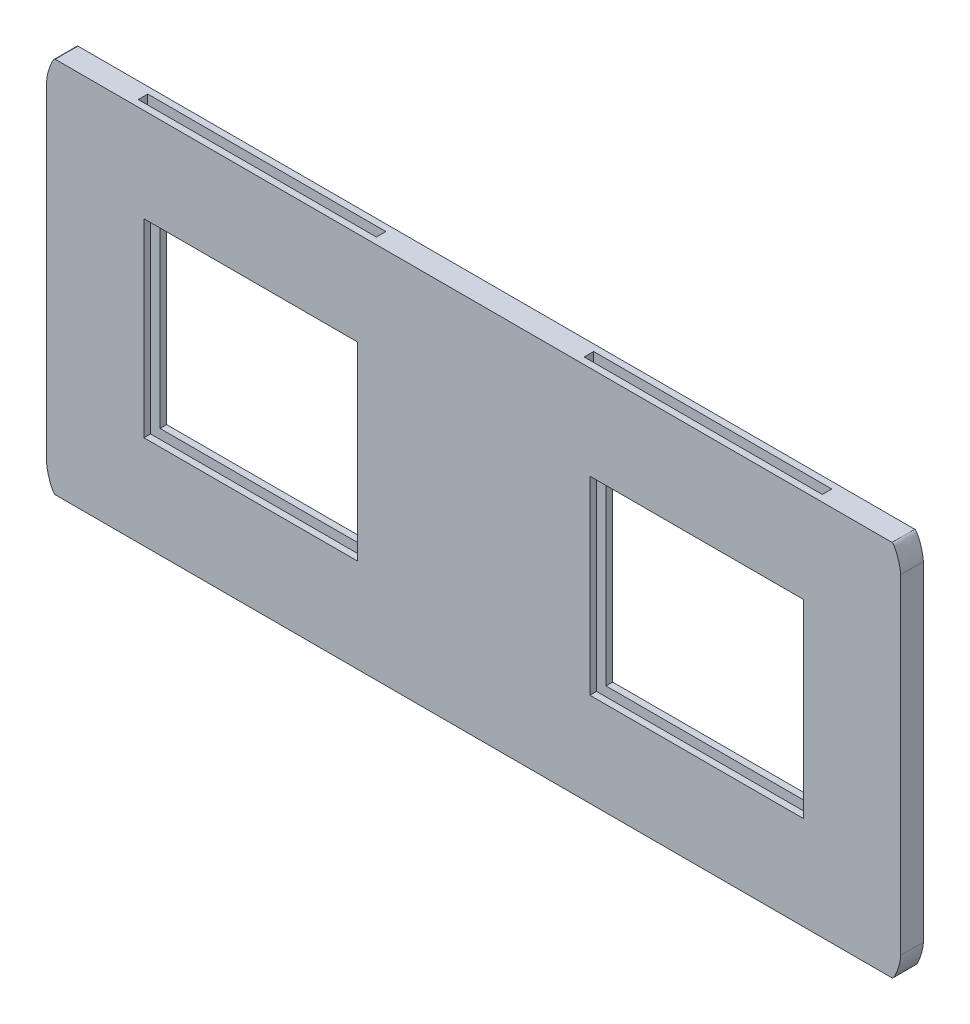
SolidWorks part; units mm, degrees
ref_plane "前视基准面" through (0, 0, 0) normal (0, 0, 1) x (1, 0, 0)
ref_plane "上视基准面" through (0, 0, 0) normal (0, 1, 0) x (1, 0, 0)
ref_plane "右视基准面" through (0, 0, 0) normal (1, 0, 0) x (0, 0, -1)
sketch "草图1" plane through (0, 0, 0) normal (0, 0, 1) x (1, 0, 0)
  line L1 (-90, 39.75) -> (90, 39.75)
  line L2 (-90, 39.75) -> (-90, -39.75)
  line L3 (-90, -39.75) -> (90, -39.75)
  line L4 (90, 39.75) -> (90, -39.75)
  line L5 (-90, 39.75) -> (90, -39.75) construction
  line L6 (-90, -39.75) -> (90, 39.75) construction
  point P0 (0, 0)
  dimension "D1" = 180
  dimension "D2" = 79.5
extrude "凸台-拉伸1" add sketch "草图1" along normal mid plane 4.8
sketch "草图2" plane through (0, 0, 2.4) normal (0, 0, 1) x (1, 0, 0)
  line L0 (0, 0) -> (0, -20.626) construction
  line L1 (-65, 12) -> (-29, 12) construction
  line L2 (-65, 12) -> (-65, -12) construction
  line L3 (-65, -12) -> (-29, -12) construction
  line L4 (-29, 12) -> (-29, -12) construction
  line L5 (-65, 12) -> (-29, -12) construction
  line L6 (-65, -12) -> (-29, 12) construction
  line L7 (65, -12) -> (29, 12) construction
  line L8 (65, 12) -> (29, -12) construction
  line L9 (29, 12) -> (29, -12) construction
  line L10 (65, -12) -> (29, -12) construction
  line L11 (65, 12) -> (65, -12) construction
  line L12 (65, 12) -> (29, 12) construction
  line L13 (-90, 39.75) -> (-90, -39.75) construction
  line L15 (-72, 25) -> (-22, 25) construction
  line L16 (-72, 25) -> (-72, -25) construction
  line L17 (-72, -25) -> (-22, -25) construction
  line L18 (-22, 25) -> (-22, -25) construction
  line L19 (-72, 25) -> (-22, -25) construction
  line L20 (-72, -25) -> (-22, 25) construction
  point P0 (-47, 0)
  point P12 (47, 0)
  point P15 (-47, 0)
  dimension "D1" = 36
  dimension "D2" = 24
  dimension "D3" = 43
  dimension "D4" = 50
sketch "草图3" plane through (0, 0, 2.4) normal (0, 0, 1) x (1, 0, 0)
  line L1 (-69.5, 20) -> (-24.5, 20)
  line L2 (-69.5, 20) -> (-69.5, -20)
  line L3 (-69.5, -20) -> (-24.5, -20)
  line L4 (-24.5, 20) -> (-24.5, -20)
  point P4 (-47, -20)
  dimension "D1" = 20
  dimension "D2" = 45
  dimension "D3" = 20
extrude "切除-拉伸1" cut sketch "草图3" against normal up to next
sketch "草图4" plane through (0, 39.75, 0) normal (0, 1, 0) x (1, 0, 0)
  line L0 (-90, -2.4) -> (-90, 2.4) construction
  line L1 (-72.1, 1) -> (-21.9, 1)
  line L2 (-72.1, 1) -> (-72.1, -1)
  line L3 (-72.1, -1) -> (-21.9, -1)
  line L4 (-21.9, 1) -> (-21.9, -1)
  line L5 (-72.1, 1) -> (-21.9, -1) construction
  line L6 (-72.1, -1) -> (-21.9, 1) construction
  point P0 (-47, 0)
  point P5 (0, 0)
  point P7 (0, 0)
  point P10 (-90, 0)
  point P11 (-57.1823, 0)
  dimension "D1" = 2
  dimension "D2" = 50.2
extrude "切除-拉伸2" cut sketch "草图4" against normal offset from surface (64.75 mm away) 25 up to plane "上视基准面" offset beyond the face yes
mirror "镜向1" about plane through (0, 0, 0) normal (1, 0, 0) of "切除-拉伸1", "切除-拉伸2"
fillet "圆角1" radius 1.8 4 edges at (90, -39.75, 0) (90, 39.75, 0) (-90, -39.75, 0) (-90, 39.75, 0) second distance 5 conic rho 0.25 first distance on face at (0, -39.75, 0) first distance on face at (0, 39.75, 0)
